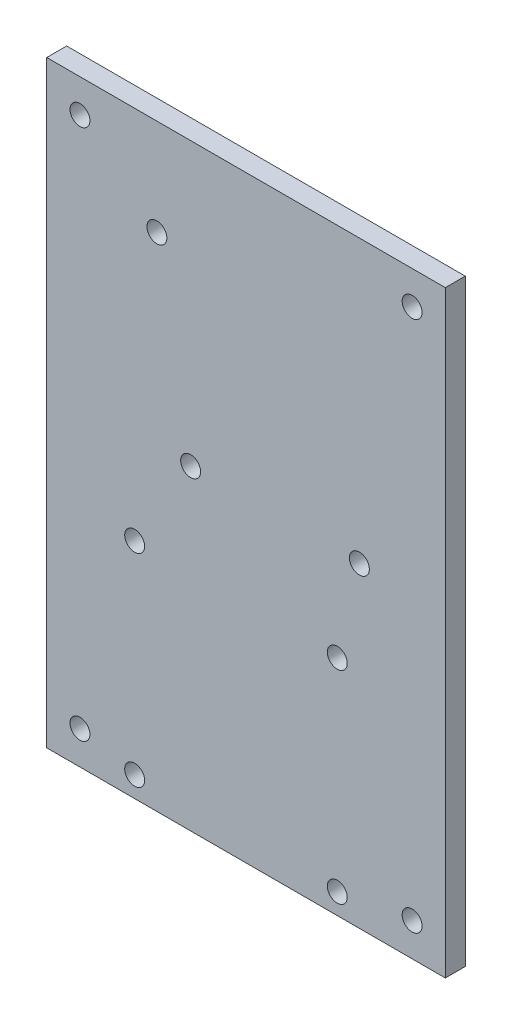
SolidWorks part; units mm, degrees
material "Custom Plastic"
ref_plane "Front Plane" through (0, 0, 0) normal (0, 0, 1) x (1, 0, 0)
ref_plane "Top Plane" through (0, 0, 0) normal (0, 1, 0) x (1, 0, 0)
ref_plane "Right Plane" through (0, 0, 0) normal (1, 0, 0) x (0, 0, -1)
sketch "Sketch1" plane through (0, 0, 0) normal (0, 0, 1) x (1, 0, 0)
  line L1 (-30, 45) -> (30, 45)
  line L2 (-30, 45) -> (-30, -45)
  line L3 (-30, -45) -> (30, -45)
  line L4 (30, 45) -> (30, -45)
  line L5 (-30, 45) -> (30, -45) construction
  line L6 (-30, -45) -> (30, 45) construction
  point P0 (0, 0)
  dimension "D1" = 60
  dimension "D2" = 90
extrude "Boss-Extrude1" add sketch "Sketch1" against normal blind 3
sketch "Sketch2" plane through (0, 0, 0) normal (0, 0, 1) x (1, 0, 0)
  line L0 (0, 0) -> (0, 45) construction
  line L1 (30, 45) -> (-30, 45) construction
  line L2 (0, 45) -> (-30, 45) construction
  line L3 (-30, 45) -> (-30, 0) construction
  line L4 (-30, 45) -> (-30, -45) construction
  line L5 (-30, 0) -> (0, 0) construction
  circle A0 centre (-25, 40) radius 1.5
  circle A1 centre (-25, -40) radius 1.5
  circle A2 centre (25, -40) radius 1.5
  circle A3 centre (25, 40) radius 1.5
  dimension "D2" = 3
  dimension "D1" = 5
  dimension "D3" = 5
extrude "Cut-Extrude1" cut sketch "Sketch2" against normal blind 3
sketch "Sketch3" plane through (0, 0, 0) normal (0, 0, 1) x (1, 0, 0)
  line L3 (17.06, 2.56) -> (-8.34, 2.56) construction
  line L4 (30, 45) -> (-30, 45) construction
  circle A0 centre (-13.42, 30.5) radius 1.5
  circle A1 centre (-8.34, 2.56) radius 1.5
  circle A2 centre (17.06, 2.56) radius 1.5
  point P0 (0, 0)
  dimension "D5" = 3
  dimension "D6" = 3
  dimension "D7" = 3
  dimension "D1" = 27.94
  dimension "D2" = 5.08
  dimension "D3" = 25.4
  dimension "D4" = 14.5
extrude "Cut-Extrude2" cut sketch "Sketch3" against normal blind 3
sketch "Sketch4" plane through (0, 0, 0) normal (0, 0, 1) x (1, 0, 0)
  line L0 (-16.7628, -11.3802) -> (-16.7628, -41.8802) construction
  line L1 (-16.7628, -41.8802) -> (13.7372, -41.8802) construction
  line L2 (13.7372, -41.8802) -> (13.7372, -11.3802) construction
  circle A0 centre (-16.7628, -41.8802) radius 1.5
  circle A1 centre (-16.7628, -11.3802) radius 1.5
  circle A2 centre (13.7372, -41.8802) radius 1.5
  circle A3 centre (13.7372, -11.3802) radius 1.5
  point P8 (-16.7628, -41.8802)
  dimension "D3" = 3
  dimension "D1" = 30.5
  dimension "D2" = 30.5
extrude "Cut-Extrude3" cut sketch "Sketch4" against normal through all
